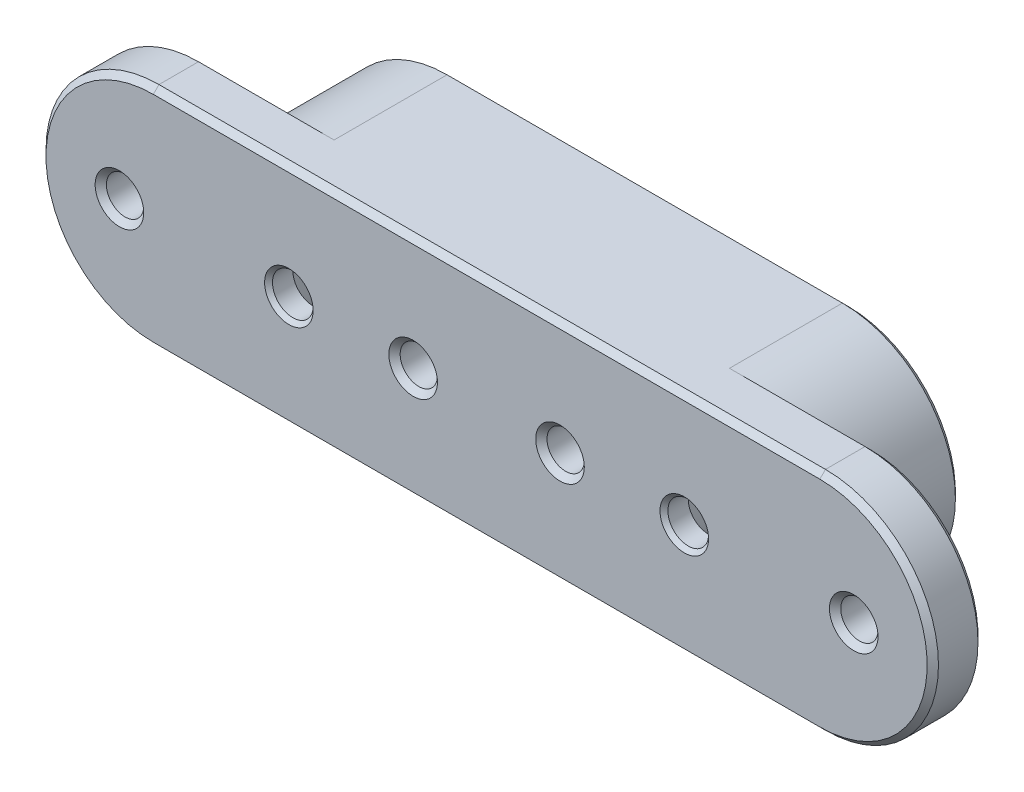
SolidWorks part; units mm, degrees
material "ABS"
ref_plane "Front Plane" through (0, 0, 0) normal (0, 0, 1) x (1, 0, 0)
ref_plane "Top Plane" through (0, 0, 0) normal (0, 1, 0) x (1, 0, 0)
ref_plane "Right Plane" through (0, 0, 0) normal (1, 0, 0) x (0, 0, -1)
sketch "Sketch1" plane through (0, 0, 0) normal (0, 0, 1) x (1, 0, 0)
  line L0 (-17.5, 0) -> (17.5, 0) construction
  line L1 (-17.5, 8) -> (17.5, 8)
  line L2 (-17.5, -8) -> (17.5, -8)
  line L3 (17.5, 0) -> (-17.5, 0) construction
  line L4 (17.5, -10) -> (-17.5, -10)
  line L5 (17.5, 10) -> (-17.5, 10)
  line L6 (29.5, 0) -> (-29.5, 0) construction
  line L7 (29.5, -10) -> (-29.5, -10)
  line L8 (29.5, 10) -> (-29.5, 10)
  arc A0 (-17.5, 8) -> (-17.5, -8) centre (-17.5, 0) ccw
  arc A1 (17.5, -8) -> (17.5, 8) centre (17.5, 0) ccw
  circle A4 centre (-17.5, 0) radius 1.65
  circle A5 centre (17.5, 0) radius 1.65
  arc A6 (17.5, -10) -> (17.5, 10) centre (17.5, 0) ccw
  arc A7 (-17.5, 10) -> (-17.5, -10) centre (-17.5, 0) ccw
  arc A8 (29.5, -10) -> (29.5, 10) centre (29.5, 0) ccw
  arc A9 (-29.5, 10) -> (-29.5, -10) centre (-29.5, 0) ccw
  circle A10 centre (32.5, 0) radius 1.65
  circle A11 centre (-32.5, 0) radius 1.65
  circle A12 centre (6.5, 0) radius 1.65
  circle A13 centre (-6.5, 0) radius 1.65
  point P2 (0, 0)
  point P16 (0, 0)
  point P21 (0, 0)
  dimension "D3" = 12
  dimension "D4" = 3.3
  dimension "D1" = 16
  dimension "D2" = 35
  dimension "D5" = 20
  dimension "D6" = 35
  dimension "D7" = 15
  dimension "D8" = 15
  dimension "D9" = 6.5
  dimension "D10" = 13
extrude "Boss-Extrude1" add sketch "Sketch1" along normal blind 4.5 contours L2 A1 L1 A0 | A4 | A5 | L5 A7 L4 A6 A1 L2 A0 L1 | L7 A8 L8 A6 A10 | L8 A9 L7 A7 A11 region at (0, 0, 0) region at (27.7973, 0, 0) region at (0, -9.4148, 0) region at (-23.5, -9.7027, 0)
extrude "Boss-Extrude2" add sketch "Sketch1<4>" against normal blind 10 contours L5 A7 L4 A6 A1 L2 A0 L1 region at (0, -9.4148, 0)
sketch "Sketch1<4>" plane through (0, 0, 0) normal (0, 0, 1) x (1, 0, 0) same geometry as "Sketch1"
chamfer "Chamfer1" distance 0.5 angle 45 30 edges at (-15.85, 0, 4.5) (19.15, 0, 4.5) (-15.85, 0, 0) (19.15, 0, 0) (0, -10, 4.5) (0, 10, 4.5) (-27.5, 0, -10) (0, -10, -10) (0, 10, -10) (27.5, 0, -10) (-25.5, 0, -10) (0, -8, -10) (0, 8, -10) (25.5, 0, -10) (39.5, 0, 4.5) (-39.5, 0, 4.5) (-23.5, 10, 0) (-23.5, -10, 0) (-39.5, 0, 0) (23.5, -10, 0) (23.5, 10, 0) (39.5, 0, 0) (34.15, 0, 0) (-30.85, 0, 0) (34.15, 0, 4.5) (-30.85, 0, 4.5) (8.15, 0, 4.5) (-4.85, 0, 4.5) (-4.85, 0, 0) (8.15, 0, 0)
hole_wizard "CSK for M3 Countersunk Flat Head Screw1" positions "Sketch2" profile "Sketch3" countersink size "M3" standard "ISO" end condition up to next
sketch "Sketch2" plane through (0, 0, 0) normal (0, 0, -1) x (-1, 0, 0)
  point P0 (-17.5, 0)
  point P3 (17.5, 0)
sketch "Sketch3" plane through (17.5, 0, 0) normal (1, 0, 0) x (0, 1, 0)
  line L0 (0, 0) -> (0, 4.5)
  line L1 (0, 4.5) -> (1.825, 4.5)
  line L2 (1.8, 4.475) -> (1.8, 2.35)
  line L3 (1.8, 2.35) -> (4.15, 0)
  line L5 (4.15, 0) -> (0, 0)
  line L6 (-1.8, 2.35) -> (-4.15, 0) construction
  line L7 (1.825, 4.5) -> (1.8, 4.475)
  line L8 (-1.825, 4.5) -> (-1.8, 4.475) construction
  line L11 (0, -6.35) -> (0, 107.95) construction
  dimension "Thru Hole Dia." = 3.6
  dimension "Thru Hole Depth" = 4.5
  dimension "Near C'Sink Dia." = 8.3
  dimension "Near C'Sink Angle" = 90
  dimension "Far C'Sink Dia." = 3.65
  dimension "Far C'Sink Angle" = 90
